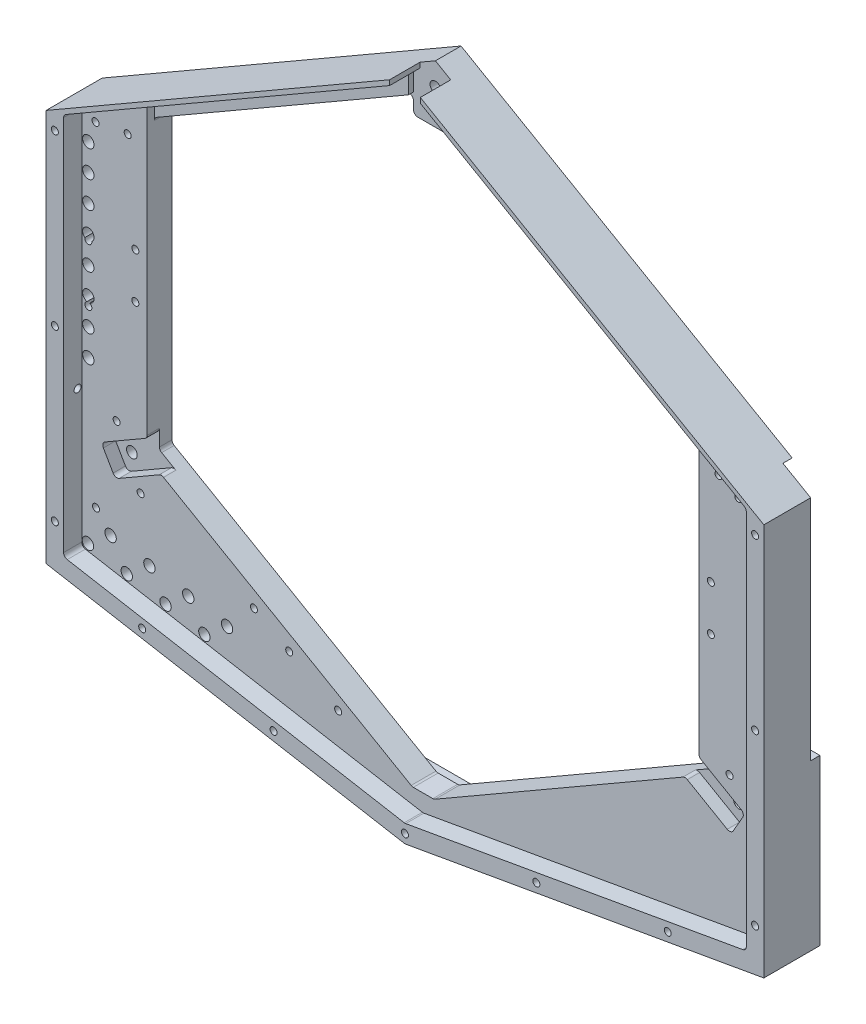
SolidWorks part; units mm, degrees
material "Copper"
ref_plane "Front Plane" through (0, 0, 0) normal (0, 0, 1) x (1, 0, 0)
ref_plane "Top Plane" through (0, 0, 0) normal (0, 1, 0) x (1, 0, 0)
ref_plane "Right Plane" through (0, 0, 0) normal (1, 0, 0) x (0, 0, -1)
sketch "Sketch2" plane through (0, 0, 0) normal (0, 0, 1) x (1, 0, 0)
  line L0 (-81.94, 26.6174) -> (0, 73.9255)
  line L1 (0, 73.9255) -> (81.94, 26.6174)
  line L2 (81.94, 26.6174) -> (81.94, -62.9963)
  line L3 (81.94, -62.9963) -> (0, -77.4445)
  line L4 (0, -77.4445) -> (-81.94, -62.9963)
  line L5 (-81.94, -62.9963) -> (-81.94, 26.6174)
  dimension "D1" = 120
  dimension "D2" = 120
  dimension "D3" = 160
  dimension "D4" = 151.37
  dimension "D5" = 163.88
extrude "Outline" add sketch "Sketch2" against normal blind 12.8
sketch "Sketch3" plane through (0, 0, 0) normal (0, 0, 1) x (1, 0, 0)
  line L0 (-77.94, 27.7721) -> (0, 72.7708)
  line L1 (0, 72.7708) -> (77.94, 27.7721)
  line L2 (77.94, 27.7721) -> (77.94, -59.6399)
  line L3 (77.94, -59.6399) -> (0, -73.3828)
  line L4 (0, -73.3828) -> (-77.94, -59.6399)
  line L5 (-77.94, -59.6399) -> (-77.94, 27.7721)
  line L12 (0, 73.9255) -> (-81.94, 26.6174) construction
  line L14 (0, -77.4445) -> (81.94, -62.9963) construction
  line L15 (-81.94, -62.9963) -> (0, -77.4445) construction
  line L16 (81.94, 26.6174) -> (0, 73.9255) construction
  line L17 (81.94, -62.9963) -> (81.94, 26.6174) construction
  line L18 (-81.94, 26.6174) -> (-81.94, -62.9963) construction
  dimension "D1" = 1
  dimension "D2" = 1
  dimension "D3" = 4
  dimension "D4" = 4
  dimension "D5" = 4
  dimension "D6" = 4
extrude "Inside Cutout" cut sketch "Sketch3" against normal blind 4.14
sketch "Reference Center Line" plane through (0, 0, -4.14) normal (0, 0, 1) x (1, 0, 0)
  line L0 (0, 73.9255) -> (0, -77.4445) construction
  line L1 (-62.3538, 35.1699) -> (0, 71.1699) construction
  line L2 (0, -70.1165) -> (62.3538, -34.1165) construction
  line L3 (62.3538, -34.1165) -> (62.3538, 37.8835) construction
  line L4 (62.3538, 37.8835) -> (0, 73.8835) construction
  line L5 (0, 73.8835) -> (-62.3538, 37.8835) construction
  line L6 (-62.3538, 37.8835) -> (-62.3538, -34.1165) construction
  line L7 (-62.3538, -34.1165) -> (0, -70.1165) construction
  line L8 (0, 71.1699) -> (62.3538, 35.1699) construction
  line L9 (-3.4641, 69.1699) -> (3.4641, 69.1699) construction
  line L11 (-46, 33.8928) -> (46, 33.8928) construction
  line L12 (-46, 33.8928) -> (-46, -62.2855) construction
  line L13 (-46, -62.2855) -> (46, -62.2855) construction
  line L14 (46, 33.8928) -> (46, -62.2855) construction
  circle A0 centre (0, 1.8835) radius 62.3538 construction
  circle A1 centre (0, 1.8835) radius 0.4741 construction
  point P22 (0, 33.8928)
  dimension "D1" = 72
  dimension "D2" = 72.042
  dimension "D3" = 2.35
  dimension "D4" = 2
  dimension "D5" = 92
sketch "Sketch5" plane through (0, 0, -12.8) normal (0, 0, -1) x (-1, 0, 0)
  line L0 (0, -70.8942) -> (-63, -34.5211)
  line L1 (-63, -34.5211) -> (-63, 31.7789)
  line L2 (5, 65.2652) -> (5, 69.884)
  line L3 (0, 0) -> (0, 50) construction
  line L6 (5, 69.884) -> (0, 72.7708)
  line L8 (0, 72.7708) -> (77.94, 27.7721) construction
  line L9 (63, 31.7789) -> (63, -34.5211)
  line L10 (63, -34.5211) -> (0, -70.8942)
  line L11 (0, 72.7708) -> (-5, 69.884)
  line L21 (5, 65.2652) -> (63, 31.7789)
  line L32 (0, 73.9255) -> (0, -77.4445) construction
  line L33 (-5, 69.884) -> (-5, 65.2652)
  line L34 (-77.94, 27.7721) -> (0, 72.7708) construction
  line L35 (-63, 31.7789) -> (-5, 65.2652)
  line L36 (0, 73.9255) -> (0, 1.8855) construction
  line L37 (0, 1.8855) -> (69.308, -38.1295) construction
  line L38 (0, 1.8855) -> (-69.308, -38.1295) construction
  dimension "D1" = 4
  dimension "D2" = 10
  dimension "D3" = 126
  dimension "D4" = 66.3
  dimension "D5" = 66.3
  dimension "D6" = 5
  dimension "D7" = 50
  dimension "D8" = 72.04
  dimension "D9" = 120
  dimension "D10" = 120
  dimension "D11" = 80.03
  dimension "D12" = 80.03
extrude "Cut for Spring Base" cut sketch "Sketch5" against normal through all
sketch "Sketch7" plane through (0, 0, -12.8) normal (0, 0, -1) x (-1, 0, 0)
  line L0 (-5, 69.884) -> (0, 72.7708)
  line L2 (0, 72.7708) -> (5, 69.884)
  line L4 (5, 69.884) -> (5, 60.7708)
  line L5 (5, 60.7708) -> (-5, 60.7708)
  line L6 (-5, 60.7708) -> (-5, 69.884)
  line L7 (-77.94, 27.7721) -> (0, 72.7708) construction
  line L8 (0, 73.9255) -> (0, -77.4445) construction
  line L9 (-77.94, 27.7721) -> (-5, 69.884) construction
  line L10 (5, 69.884) -> (77.94, 27.7721) construction
  dimension "D2" = 12
  dimension "D3" = 10
extrude "J Flex Mounting Point" add sketch "Sketch7" against normal offset from surface (5.85 mm away) 2.81 up to face at (0, 4.0573, -4.14)
sketch "Sketch6" plane through (0, 0, -12.8) normal (0, 0, -1) x (-1, 0, 0)
  line L0 (-67.5, 33.7996) -> (-67.5, -37.6965)
  line L2 (10, -70.8942) -> (67.5, -37.6965)
  line L3 (67.5, -37.6965) -> (67.5, 33.7996)
  line L9 (-10, -70.8942) -> (0, -70.8942)
  line L10 (-63, 31.7789) -> (-63, -34.5211) construction
  line L11 (63, -34.5211) -> (63, 31.7789) construction
  line L12 (0, -70.8942) -> (63, -34.5211) construction
  line L19 (67.5, 33.7996) -> (0, 72.7708)
  line L20 (77.94, 27.7721) -> (0, 72.7708) construction
  line L21 (0, 72.7708) -> (-77.94, 27.7721) construction
  line L22 (0, 72.7708) -> (-67.5, 33.7996)
  line L47 (0, -70.8942) -> (10, -70.8942)
  line L48 (-67.5, -37.6965) -> (-10, -70.8942)
  line L50 (-63, -34.5211) -> (0, -70.8942) construction
  line L52 (0, 73.9255) -> (0, -77.4445) construction
  dimension "D1" = 4.5
  dimension "D2" = 4.5
  dimension "D3" = 5
  dimension "D4" = 5
extrude "Spring Base Mounting Cut" cut sketch "Sketch6" against normal blind 3
sketch "Sketch9" plane through (0, 0, 0) normal (0, 0, 1) x (1, 0, 0)
  line L2 (3.5, 71.9048) -> (3.5, 70.7501)
  line L3 (77.94, 27.7721) -> (0, 72.7708) construction
  line L4 (3.5, 70.7501) -> (0, 72.7708)
  line L5 (0, 72.7708) -> (-3.5, 70.7501)
  line L6 (0, 72.7708) -> (-77.94, 27.7721) construction
  line L7 (-3.5, 70.7501) -> (-3.5, 71.9048)
  line L10 (-3.5, 71.9048) -> (0, 73.9255)
  line L11 (0, 73.9255) -> (0, -77.4445) construction
  line L12 (0, 73.9255) -> (3.5, 71.9048)
  line L14 (0, 73.9255) -> (-81.94, 26.6174) construction
  dimension "D1" = 7
extrude "Central Copper Flex cutout" cut sketch "Sketch9" against normal up to surface (6.95 mm away) up to face at (0, 66.373, -6.95)
hole_wizard "M2 Tap Drill for Backplate" positions "Sketch10" profile "Sketch11" hole size "M2x0.4" standard "ANSI Metric"
sketch "Sketch10" plane through (0, 0, -9.8) normal (0, 0, -1) x (-1, 0, 0)
  line L0 (-65, 24.3042) -> (-65, -35.6758) construction
  line L1 (-65, -35.6758) -> (-4, -70.8942) construction
  line L2 (-10, -70.8942) -> (10, -70.8942) construction
  line L4 (4, -70.8942) -> (65, -35.6758) construction
  line L5 (65, -35.6758) -> (65, 24.3242) construction
  line L7 (-63, -34.5211) -> (-63, 31.7789) construction
  line L8 (63, 31.7789) -> (63, -34.5211) construction
  line L9 (63, -34.5211) -> (0, -70.8942) construction
  line L10 (0, -70.8942) -> (-63, -34.5211) construction
  line L29 (-62.3538, 33.884) -> (0, 69.884) construction
  line L30 (-62.3538, -34.1165) -> (-62.3538, 37.8835) construction
  line L31 (0, 73.9255) -> (0, -77.4445) construction
  line L32 (0, 69.884) -> (62.3538, 33.884) construction
  line L33 (62.3538, 37.8835) -> (62.3538, -34.1165) construction
  line L36 (5, 65.2652) -> (63, 31.7789) construction
  line L37 (-63, 31.7789) -> (-5, 65.2652) construction
  line L38 (-63, -34.5211) -> (-67.5, -37.6965) construction
  point P0 (-65, 24.3042)
  point P2 (-41.1362, 46.134)
  point P4 (-19.4856, 58.634)
  point P6 (19.4856, 58.634)
  point P8 (41.1362, 46.134)
  point P10 (65, 24.3242)
  point P12 (65, 1.8242)
  point P14 (65, -20.6758)
  point P18 (52.0096, -43.1758)
  point P20 (32.9571, -54.1758)
  point P22 (15.6366, -64.1758)
  point P24 (-15.6366, -64.1758)
  point P26 (-32.9571, -54.1758)
  point P28 (-52.0096, -43.1758)
  point P32 (-65, -20.6958)
  point P35 (-65, 1.8042)
  dimension "D1" = 2
  dimension "D2" = 2
  dimension "D3" = 2
  dimension "D4" = 2
  dimension "D5" = 14.98
  dimension "D6" = 22.5
  dimension "D7" = 22.5
  dimension "D8" = 15
  dimension "D9" = 22
  dimension "D10" = 20
  dimension "D11" = 20
  dimension "D12" = 22
  dimension "D13" = 15
  dimension "D14" = 22.5
  dimension "D15" = 22.5
  dimension "D16" = 15
  dimension "D17" = 1.5
  dimension "D18" = 22.5
  dimension "D19" = 25
  dimension "D20" = 22.5
  dimension "D21" = 25
sketch "Sketch11" plane through (65, 24.3042, -9.8) normal (1, 0, 0) x (0, 1, 0)
  line L0 (0, 0) -> (0, 3.9807)
  line L1 (0, 3.9807) -> (0.8, 3.5)
  line L2 (0.8, 3.5) -> (0.8, 0)
  line L5 (0.8, 0) -> (0, 0)
  line L10 (0, 3.9807) -> (-0.8, 3.5) construction
  line L11 (0, -6.35) -> (0, 107.95) construction
  dimension "Hole Dia." = 1.6
  dimension "Hole Depth" = 3.5
  dimension "Drill Angle" = 118
sketch "Sketch12" plane through (0, 0, -12.8) normal (0, 0, -1) x (-1, 0, 0)
  line L0 (10, -70.8942) -> (67.5, -37.6965) construction
  line L1 (64, -39.7172) -> (67.5, -37.6965)
  line L2 (67.5, -37.6965) -> (67.5, -33.6551)
  line L3 (67.5, -37.6965) -> (67.5, 33.7996) construction
  line L4 (67.5, -33.6551) -> (74.4462, -37.6654)
  line L5 (74.4462, -37.6654) -> (70.9462, -43.7276)
  line L6 (70.9462, -43.7276) -> (64, -39.7172)
  line L7 (-67.5, -33.6551) -> (-67.5, -37.6965)
  line L8 (-67.5, 33.7996) -> (-67.5, -37.6965) construction
  line L9 (-67.5, -37.6965) -> (-64, -39.7172)
  line L10 (-67.5, -37.6965) -> (-10, -70.8942) construction
  line L11 (-64, -39.7172) -> (-70.9462, -43.7276)
  line L12 (-70.9462, -43.7276) -> (-74.4462, -37.6654)
  line L13 (-74.4462, -37.6654) -> (-67.5, -33.6551)
  dimension "D1" = 60
  dimension "D2" = 6
  dimension "D3" = 7
  dimension "D4" = 6
  dimension "D5" = 7
extrude "Outer Copper Flex cutouts" cut sketch "Sketch12" against normal up to surface (3 mm away) up to face at (64.2, 24.3042, -9.8)
hole_wizard "#2 Clearance Holes for Flex Feet" positions "Sketch13" profile "Sketch14" hole size "#2" standard "ANSI Inch" end condition up to next
sketch "Sketch13" plane through (0, 0, -9.8) normal (0, 0, -1) x (-1, 0, 0)
  line L1 (0, 1.8835) -> (69.3037, -38.129) construction
  line L3 (0, 1.8835) -> (-69.308, -38.1315) construction
  line L5 (0, 73.9255) -> (0, -77.4445) construction
  point P0 (69.3037, -38.129)
  point P3 (-69.308, -38.1315)
  point P6 (0, 68.6855)
  dimension "D1" = 66.802
  dimension "D2" = 80.025
  dimension "D3" = 60
  dimension "D4" = 60
  dimension "D5" = 80.03
sketch "Sketch14" plane through (-69.3037, -38.129, -9.8) normal (1, 0, 0) x (0, 1, 0)
  line L0 (0, 0) -> (0, 5.66)
  line L1 (0, 5.66) -> (1.2192, 5.66)
  line L2 (1.2192, 5.66) -> (1.2192, 0)
  line L5 (1.2192, 0) -> (0, 0)
  line L11 (0, -6.35) -> (0, 107.95) construction
  dimension "Thru Hole Dia." = 2.4384
  dimension "Thru Hole Depth" = 5.66
sketch "Sketch15" plane through (0, 0, -4.14) normal (0, 0, 1) x (1, 0, 0)
  line L0 (-63, -30.7945) -> (-73.5018, -36.8577)
  line L1 (-63, 31.7789) -> (-63, -34.5211) construction
  line L2 (-73.5018, -36.8577) -> (-70.2745, -42.4476)
  line L3 (-70.2745, -42.4476) -> (-59.7727, -36.3844)
  line L4 (-63, -34.5211) -> (0, -70.8942) construction
  line L5 (-59.7727, -36.3844) -> (-63, -34.5211)
  line L6 (-63, -34.5211) -> (-63, -30.7945)
  line L7 (-64.6136, -31.7262) -> (-61.3864, -37.316) construction
  line L8 (63, -34.5211) -> (63, -30.8575)
  line L9 (63, -34.5211) -> (63, 31.7789) construction
  line L10 (63, -30.8575) -> (73.4788, -36.9075)
  line L11 (73.4788, -36.9075) -> (70.3061, -42.4028)
  line L12 (70.3061, -42.4028) -> (59.8273, -36.3529)
  line L13 (0, -70.8942) -> (63, -34.5211) construction
  line L14 (59.8273, -36.3529) -> (63, -34.5211)
  point P12 (-63, -34.5211)
  dimension "D1" = 3.2
  dimension "D2" = 3
  dimension "D3" = 3.2
  dimension "D4" = 3
extrude "Channels for Outer Flex" cut sketch "Sketch15" against normal up to surface (2.81 mm away) up to face at (1.2192, 68.6855, -6.95)
sketch "Sketch17" plane through (0, 0, -9.8) normal (0, 0, -1) x (-1, 0, 0)
  line L0 (-65, 1.8042) -> (-65, -20.6958) construction
  line L1 (65, -20.6758) -> (65, 1.8242) construction
  circle A0 centre (-65, -9.4458) radius 0.8
  circle A1 centre (65, -9.4258) radius 0.8
  dimension "D1" = 1.6
  dimension "D2" = 1.6
extrude "Optional Alignment Pins" cut sketch "Sketch17" against normal blind 3
sketch "SMA Reference Sketch" plane through (0, 0, -12.8) normal (0, 0, -1) x (-1, 0, 0)
  line L14 (81.94, 26.6174) -> (81.94, -62.9963) construction
  line L21 (73.8944, 19.163) -> (78.9856, 14.0718) construction
  line L22 (73.8944, 23.663) -> (78.9856, 18.5718) construction
  line L23 (73.8944, 14.663) -> (78.9856, 9.5718) construction
  line L24 (73.8944, 10.163) -> (78.9856, 5.0718) construction
  line L25 (72.1444, -32.8014) -> (77.2356, -37.8926) construction
  line L26 (-73.8944, 20.0718) -> (-78.9856, 25.163) construction
  line L27 (-81.94, -62.9963) -> (-81.94, 26.6174) construction
  line L28 (-73.8944, 15.5718) -> (-78.9856, 20.663) construction
  line L29 (-73.8944, 11.0718) -> (-78.9856, 16.163) construction
  line L30 (-73.8944, 6.5718) -> (-78.9856, 11.663) construction
  line L31 (59.1444, -57.3926) -> (64.2356, -52.3014) construction
  line L32 (72.1444, -50.8926) -> (77.2356, -45.8014) construction
  line L33 (72.1444, -93.8926) -> (77.2356, -88.8014) construction
  line L34 (-73.8944, 2.0718) -> (-78.9856, 7.163) construction
  line L35 (-73.8944, -2.4282) -> (-78.9856, 2.663) construction
  line L36 (-73.8944, -6.9282) -> (-78.9856, -1.837) construction
  line L37 (-73.8944, -11.4282) -> (-78.9856, -6.337) construction
  line L38 (73.8944, 5.663) -> (78.9856, 0.5718) construction
  line L39 (73.8944, 1.163) -> (78.9856, -3.9282) construction
  line L40 (73.8944, -3.337) -> (78.9856, -8.4282) construction
  line L41 (73.8944, -7.837) -> (78.9856, -12.9282) construction
  circle A0 centre (73.8944, 23.663) radius 0.95 construction
  circle A1 centre (78.9856, 18.5718) radius 0.95 construction
  circle A2 centre (76.44, 21.1174) radius 1.3 construction
  circle A3 centre (73.8944, 19.163) radius 0.95 construction
  circle A4 centre (78.9856, 14.0718) radius 0.95 construction
  circle A5 centre (76.44, 16.6174) radius 1.3 construction
  circle A6 centre (73.8944, 14.663) radius 0.95 construction
  circle A7 centre (78.9856, 9.5718) radius 0.95 construction
  circle A8 centre (76.44, 12.1174) radius 1.3 construction
  circle A9 centre (73.8944, 10.163) radius 0.95 construction
  circle A10 centre (78.9856, 5.0718) radius 0.95 construction
  circle A11 centre (76.44, 7.6174) radius 1.3 construction
  circle A12 centre (72.1444, -32.8014) radius 0.95 construction
  circle A13 centre (77.2356, -37.8926) radius 0.95 construction
  circle A14 centre (74.69, -35.347) radius 1.3 construction
  circle A15 centre (-76.44, 22.6174) radius 1.3 construction
  circle A16 centre (-78.9856, 25.163) radius 0.95 construction
  circle A17 centre (-73.8944, 20.0718) radius 0.95 construction
  circle A18 centre (-76.44, 18.1174) radius 1.3 construction
  circle A19 centre (-78.9856, 20.663) radius 0.95 construction
  circle A20 centre (-73.8944, 15.5718) radius 0.95 construction
  circle A21 centre (-76.44, 13.6174) radius 1.3 construction
  circle A22 centre (-78.9856, 16.163) radius 0.95 construction
  circle A23 centre (-73.8944, 11.0718) radius 0.95 construction
  circle A24 centre (-76.44, 9.1174) radius 1.3 construction
  circle A25 centre (-78.9856, 11.663) radius 0.95 construction
  circle A26 centre (-73.8944, 6.5718) radius 0.95 construction
  circle A27 centre (61.69, -54.847) radius 1.3 construction
  circle A28 centre (64.2356, -52.3014) radius 0.95 construction
  circle A29 centre (59.1444, -57.3926) radius 0.95 construction
  circle A30 centre (72.1444, -50.8926) radius 0.95 construction
  circle A31 centre (77.2356, -45.8014) radius 0.95 construction
  circle A32 centre (74.69, -48.347) radius 1.3 construction
  circle A33 centre (74.69, -91.347) radius 1.3 construction
  circle A34 centre (77.2356, -88.8014) radius 0.95 construction
  circle A35 centre (72.1444, -93.8926) radius 0.95 construction
  circle A36 centre (74.69, -35.347) radius 43 construction
  circle A37 centre (74.69, -48.347) radius 13 construction
  circle A38 centre (61.69, -54.847) radius 43 construction
  circle A39 centre (74.69, -91.347) radius 43 construction
  circle A40 centre (76.44, 21.1174) radius 13 construction
  circle A41 centre (-76.44, 4.6174) radius 1.3 construction
  circle A42 centre (-78.9856, 7.163) radius 0.95 construction
  circle A43 centre (-73.8944, 2.0718) radius 0.95 construction
  circle A44 centre (-76.44, 0.1174) radius 1.3 construction
  circle A45 centre (-78.9856, 2.663) radius 0.95 construction
  circle A46 centre (-73.8944, -2.4282) radius 0.95 construction
  circle A47 centre (-76.44, -4.3826) radius 1.3 construction
  circle A48 centre (-78.9856, -1.837) radius 0.95 construction
  circle A49 centre (-73.8944, -6.9282) radius 0.95 construction
  circle A50 centre (-76.44, -8.8826) radius 1.3 construction
  circle A51 centre (-78.9856, -6.337) radius 0.95 construction
  circle A52 centre (-73.8944, -11.4282) radius 0.95 construction
  circle A53 centre (73.8944, 5.663) radius 0.95 construction
  circle A54 centre (78.9856, 0.5718) radius 0.95 construction
  circle A55 centre (76.44, 3.1174) radius 1.3 construction
  circle A56 centre (73.8944, 1.163) radius 0.95 construction
  circle A57 centre (78.9856, -3.9282) radius 0.95 construction
  circle A58 centre (76.44, -1.3826) radius 1.3 construction
  circle A59 centre (73.8944, -3.337) radius 0.95 construction
  circle A60 centre (78.9856, -8.4282) radius 0.95 construction
  circle A61 centre (76.44, -5.8826) radius 1.3 construction
  circle A62 centre (73.8944, -7.837) radius 0.95 construction
  circle A63 centre (78.9856, -12.9282) radius 0.95 construction
  circle A64 centre (76.44, -10.3826) radius 1.3 construction
  point P10 (76.44, 16.6174)
  point P20 (76.44, 21.1174)
  point P25 (76.44, 12.1174)
  point P32 (76.44, 7.6174)
  point P37 (74.69, -35.347)
  point P120 (76.44, 3.1174)
  point P127 (76.44, -1.3826)
  point P134 (76.44, -5.8826)
  point P141 (76.44, -10.3826)
  dimension "D5" = 1.9
  dimension "D2" = 2.6
  dimension "D3" = 8
  dimension "D10" = 2.6
  dimension "D11" = 1.9
  dimension "D12" = 1.9
  dimension "D18" = 26
  dimension "D23" = 86
  dimension "D26" = 4.5
  dimension "D27" = 4.5
  dimension "D28" = 4.5
  dimension "D29" = 43
  dimension "D30" = 13
  dimension "D31" = 26
  dimension "D1" = 7.2
  dimension "D4" = 4.5
  dimension "D6" = 5.5
  dimension "D7" = 5.5
  dimension "D8" = 45
  dimension "D9" = 7.25
  dimension "D13" = 7.2
  dimension "D14" = 5.5
  dimension "D15" = 4
  dimension "D16" = 45
  dimension "D19" = 7.25
  dimension "D20" = 45
  dimension "D21" = 4.5
  dimension "D22" = 7.25
  dimension "D24" = 13
  dimension "D25" = 43
  dimension "D17" = 8
sketch "Sketch19" plane through (0, 0, -12.8) normal (0, 0, -1) x (-1, 0, 0)
  line L1 (81.94, -62.9963) -> (0, -77.4445) construction
  circle A0 centre (76.44, 21.1174) radius 1.3
  circle A12 centre (-76.44, 22.6174) radius 1.3
  circle A22 centre (-76.44, 16.5174) radius 1.3
  circle A23 centre (-76.44, 10.4174) radius 1.3
  circle A24 centre (-76.44, 4.3174) radius 1.3
  circle A25 centre (-76.44, -1.7826) radius 1.3
  circle A26 centre (-76.44, -7.8826) radius 1.3
  circle A27 centre (-76.44, -13.9826) radius 1.3
  circle A28 centre (-76.44, -20.0826) radius 1.3
  circle A29 centre (76.44, 15.0174) radius 1.3
  circle A30 centre (76.44, 8.9174) radius 1.3
  circle A31 centre (76.44, 2.8174) radius 1.3
  circle A32 centre (76.44, -3.2826) radius 1.3
  circle A33 centre (76.44, -9.3826) radius 1.3
  circle A34 centre (76.44, -15.4826) radius 1.3
  circle A35 centre (76.44, -21.5826) radius 1.3
  circle A36 centre (49.94, -63.0539) radius 1.3
  circle A44 centre (44.763, -58.8896) radius 1.3
  circle A50 centre (53.6263, -57.3268) radius 1.3
  circle A51 centre (58.8033, -61.4911) radius 1.3
  circle A52 centre (62.4895, -55.7639) radius 1.3
  circle A53 centre (67.6665, -59.9282) radius 1.3
  circle A54 centre (71.3528, -54.2011) radius 1.3
  circle A55 centre (76.5298, -58.3654) radius 1.3
  dimension "D1" = 2.6
  dimension "D2" = 8
  dimension "D3" = 8
  dimension "D4" = 5.5
  dimension "D5" = 32
  dimension "D6" = 4
  dimension "D7" = 10.5
  dimension "D8" = 6.644
extrude "SMA_Lines" cut sketch "Sketch19" against normal up to next
sketch "Sketch20" plane through (0, 0, -12.8) normal (0, 0, -1) x (-1, 0, 0)
  line L0 (67.5, 23.8447) -> (73.0812, 29.4259)
  line L1 (67.5, -33.6551) -> (67.5, 33.7996) construction
  line L2 (42.44, -52.1649) -> (37.6769, -54.9149)
  line L3 (73.0812, 29.4259) -> (81.94, 20.5672)
  line L4 (81.94, 20.5672) -> (81.94, -62.9963)
  line L5 (81.94, -62.9963) -> (42.44, -69.9612)
  line L6 (81.94, -62.9963) -> (0, -77.4445) construction
  line L8 (10, -70.8942) -> (64, -39.7172) construction
  line L9 (10, -70.8942) -> (64, -39.7172) construction
  line L10 (42.44, -52.1649) -> (64, -39.7172)
  line L11 (64, -39.7172) -> (67.5, -33.6551)
  line L12 (67.5, -33.6551) -> (74.4462, -37.6654) construction
  line L13 (67.5, -33.6551) -> (67.5, 23.8447)
  line L14 (-75.6096, 30.2723) -> (-67.5, 22.1627)
  line L15 (-81.94, 26.6174) -> (0, 73.9255) construction
  line L16 (-67.5, 33.7996) -> (-67.5, -33.6551) construction
  line L17 (-67.5, 22.1627) -> (-67.5, -25.3826)
  line L18 (-67.5, -25.3826) -> (-81.94, -25.3826)
  line L20 (-81.94, -62.9963) -> (-81.94, 26.6174) construction
  line L21 (-81.94, -25.3826) -> (-81.94, 26.6174)
  line L22 (-81.94, 26.6174) -> (-75.6096, 30.2723)
  line L23 (73.8944, 23.663) -> (78.9856, 18.5718) construction
  line L24 (-73.8944, 20.0718) -> (-78.9856, 25.163) construction
  line L25 (37.6769, -54.9149) -> (37.6769, -58.9149)
  line L26 (37.6769, -58.9149) -> (42.44, -58.9149)
  line L28 (42.44, -58.9149) -> (42.44, -69.9612)
  dimension "D2" = 8.25
  dimension "D3" = 6
  dimension "D4" = 34.5
  dimension "D5" = 3.5
extrude "SMA Cutaway" cut sketch "Sketch20" against normal offset from surface (2.11 mm away) 6.55 up to face at (77.74, 22.6174, -4.14)
fillet "Fillet4" radius 3 2 edges at (-73.0812, 29.4259, -11.745) (-37.6769, -58.9149, -11.745)
hole_wizard "M2x0.4 Tapped for SMAs" positions "Sketch21" profile "Sketch22" hole size "M2x0.4" standard "ANSI Metric"
sketch "Sketch21" plane through (0, 0, -10.69) normal (0, 0, -1) x (-1, 0, 0)
  circle A0 centre (76.44, 21.1174) radius 1.3 construction
  circle A1 centre (-76.44, 22.6174) radius 1.3 construction
  circle A2 centre (49.94, -63.0539) radius 1.3 construction
  circle A3 centre (44.763, -58.8896) radius 1.3 construction
  point P72 (73.895, 23.6624)
  point P74 (78.985, 18.5724)
  point P90 (-78.985, 25.1624)
  point P92 (-73.895, 20.0724)
  point P108 (-78.985, 19.0624)
  point P109 (-73.895, 13.9724)
  point P110 (-78.985, 12.9624)
  point P111 (-73.895, 7.8724)
  point P112 (-78.985, 6.8624)
  point P113 (-73.895, 1.7724)
  point P114 (-78.985, 0.7624)
  point P115 (-73.895, -4.3276)
  point P116 (-78.985, -5.3376)
  point P117 (-73.895, -10.4276)
  point P118 (-78.985, -11.4376)
  point P119 (-73.895, -16.5276)
  point P120 (-78.985, -17.5376)
  point P121 (-73.895, -22.6276)
  point P138 (73.895, 17.5624)
  point P139 (78.985, 12.4724)
  point P140 (73.895, 11.4624)
  point P141 (78.985, 6.3724)
  point P142 (73.895, 5.3624)
  point P143 (78.985, 0.2724)
  point P144 (73.895, -0.7376)
  point P145 (78.985, -5.8276)
  point P146 (73.895, -6.8376)
  point P147 (78.985, -11.9276)
  point P148 (73.895, -12.9376)
  point P149 (78.985, -18.0276)
  point P150 (73.895, -19.0376)
  point P151 (78.985, -24.1276)
  point P171 (49.315, -59.5089)
  point P173 (50.565, -66.5989)
  point P185 (58.1783, -57.9461)
  point P186 (59.4283, -65.0361)
  point P187 (67.0415, -56.3832)
  point P188 (68.2915, -63.4732)
  point P189 (75.9048, -54.8204)
  point P190 (77.1548, -61.9104)
  point P191 (45.388, -62.4346)
  point P193 (44.138, -55.3446)
  point P202 (54.2513, -60.8718)
  point P203 (53.0013, -53.7818)
  point P204 (63.1145, -59.3089)
  point P205 (61.8645, -52.2189)
  point P206 (71.9778, -57.7461)
  point P207 (70.7278, -50.6561)
  dimension "D4" = 2.545
  dimension "D7" = 2.545
  dimension "D8" = 2.545
  dimension "D9" = 8
  dimension "D14" = 0.625
  dimension "D1" = 2.545
  dimension "D2" = 2.545
  dimension "D3" = 2.545
  dimension "D5" = 2.545
  dimension "D6" = 2.545
  dimension "D11" = 3.545
  dimension "D12" = 0.625
  dimension "D13" = 3.545
  dimension "D16" = 3.545
  dimension "D17" = 0.625
  dimension "D18" = 0.625
  dimension "D19" = 3.545
  dimension "D10" = 8
  dimension "D15" = 4
sketch "Sketch22" plane through (-73.895, 23.6624, -10.69) normal (1, 0, 0) x (0, 1, 0)
  line L0 (0, 0) -> (0, 5.4807)
  line L1 (0, 5.4807) -> (0.8, 5)
  line L2 (0.8, 5) -> (0.8, 0)
  line L5 (0.8, 0) -> (0, 0)
  line L10 (0, 5.4807) -> (-0.8, 5) construction
  line L11 (0, -6.35) -> (0, 107.95) construction
  dimension "Hole Dia." = 1.6
  dimension "Hole Depth" = 5
  dimension "Drill Angle" = 118
sketch "Sketch23" plane through (0, 0, -4.14) normal (0, 0, 1) x (1, 0, 0)
  line L0 (-63, 31.7789) -> (-63, 36.3977)
  line L1 (-3.5, 70.7501) -> (-77.94, 27.7721) construction
  line L2 (-63, 36.3977) -> (-5, 69.884)
  line L3 (-5, 69.884) -> (-5, 65.2652)
  line L4 (-5, 65.2652) -> (-63, 31.7789)
  line L5 (5, 65.2652) -> (5, 69.884)
  line L6 (5, 65.2652) -> (63, 31.7789)
  line L7 (63, 31.7789) -> (63, 36.3977)
  line L8 (77.94, 27.7721) -> (5, 69.884) construction
  line L9 (63, 36.3977) -> (5, 69.884)
extrude "Slight Relief Under Array" cut sketch "Sketch23" against normal blind 1.66
hole_wizard "M2x0.4 Tapped for Radiation Cover" positions "Sketch24" profile "Sketch25" hole size "M2x0.4" standard "ANSI Metric"
sketch "Sketch24" plane through (0, 0, 0) normal (0, 0, 1) x (1, 0, 0)
  line L0 (-81.94, 26.6174) -> (-81.94, -62.9963) construction
  line L1 (-77.94, -59.6399) -> (0, -73.3828) construction
  line L2 (0, -73.3828) -> (77.94, -59.6399) construction
  line L3 (77.94, -59.6399) -> (77.94, 27.7721) construction
  line L4 (81.94, -62.9963) -> (81.94, 26.6174) construction
  line L5 (-79.94, 23.6174) -> (-79.94, -53.6399) construction
  line L6 (0, -77.4445) -> (0, -73.3828) construction
  line L7 (79.94, 23.6174) -> (79.94, -53.6399) construction
  line L8 (0, -73.3828) -> (77.94, -59.6399) construction
  point P0 (-79.94, 23.6174)
  point P2 (-79.94, -53.6399)
  point P4 (-30, -70.1239)
  point P6 (30, -70.1239)
  point P8 (79.94, -53.6399)
  point P10 (79.94, 23.6174)
  point P31 (-79.94, -15.0112)
  point P38 (0, -75.4137)
  point P44 (79.94, -15.0112)
  point P47 (-60, -64.834)
  point P49 (60, -64.834)
  dimension "D1" = 2
  dimension "D2" = 3
  dimension "D3" = 2
  dimension "D4" = 6
  dimension "D5" = 2
  dimension "D6" = 30
  dimension "D7" = 2
  dimension "D8" = 30
  dimension "D9" = 2
  dimension "D10" = 6
  dimension "D11" = 2
  dimension "D12" = 3
  dimension "D13" = 2
  dimension "D14" = 30
  dimension "D15" = 2
  dimension "D16" = 30
sketch "Sketch25" plane through (-79.94, 23.6174, 0) normal (1, 0, 0) x (0, -1, 0)
  line L0 (0, 0) -> (0, 5.4807)
  line L1 (0, 5.4807) -> (0.8, 5)
  line L2 (0.8, 5) -> (0.8, 0)
  line L5 (0.8, 0) -> (0, 0)
  line L10 (0, 5.4807) -> (-0.8, 5) construction
  line L11 (0, -6.35) -> (0, 107.95) construction
  dimension "Hole Dia." = 1.6
  dimension "Hole Depth" = 5
  dimension "Drill Angle" = 118
hole_wizard "M2x0.4 Tap for PCB Mounts" positions "Sketch26" profile "Sketch27" hole size "M2x0.4" standard "ANSI Metric"
sketch "Sketch26" plane through (0, 0, -4.14) normal (0, 0, 1) x (1, 0, 0)
  line L1 (76.44, 22.6174) -> (76.44, 2.1174) construction
  line L6 (74.69, -6.3826) -> (74.69, -18.8826) construction
  line L9 (-76.44, 21.1174) -> (-76.44, 8.1174) construction
  line L11 (-76.44, -4.8826) -> (-76.44, -17.8826) construction
  line L15 (-76.44, -11.3826) -> (-77.94, -11.3826) construction
  line L16 (-77.94, 27.7721) -> (-77.94, -59.6399) construction
  line L18 (-76.44, 14.6174) -> (-77.94, 14.6174) construction
  line L19 (-77.94, 27.7721) -> (-77.94, -59.6399) construction
  line L23 (-76.44, 8.1174) -> (-76.44, -4.8826) construction
  line L24 (-74.69, -56.8826) -> (-74.69, -43.8826) construction
  circle A6 centre (76.44, 22.6174) radius 1.3 construction
  circle A11 centre (-76.44, 21.1174) radius 1.3 construction
  point P0 (76.44, 12.3674)
  point P20 (76.44, 12.3674)
  point P31 (74.69, -12.6326)
  point P34 (74.69, -12.6326)
  point P53 (-76.44, 14.6174)
  point P55 (-76.44, -11.3826)
  point P57 (-74.69, -50.3826)
  point P59 (-19.3942, -62.8516)
  point P78 (-76.44, 14.6174)
  point P79 (-76.44, -11.3826)
  point P95 (-76.44, 1.6174)
  point P106 (-67.45, 27.1118)
  point P108 (-65.6984, 5.1456)
  point P110 (-65.6984, -5.1874)
  point P112 (-69.9656, -30.8826)
  point P114 (-64.5046, -42.4348)
  point P116 (-38.622, -52.2344)
  point P118 (-30.5702, -56.7556)
  point P140 (71.9662, 24.8501)
  point P150 (74.69, -0.1326)
  point P153 (69.97, -30.8826)
  point P159 (67.45, 27.1118)
  point P161 (65.7, 5.1456)
  point P163 (65.7, -5.1874)
  point P174 (-74.7882, 25.8367)
  dimension "D8" = 0.3048
  dimension "D11" = 10.1854
  dimension "D2" = 5
  dimension "D3" = 8.99
  dimension "D4" = 5.9944
  dimension "D7" = 2.9718
  dimension "8.99" = 8.99
  dimension "D22" = 0
  dimension "D23" = 5
sketch "Sketch27" plane through (76.44, 12.3674, -4.14) normal (1, 0, 0) x (0, -1, 0)
  line L0 (0, 0) -> (0, 5.1807)
  line L1 (0, 5.1807) -> (0.8, 4.7)
  line L2 (0.8, 4.7) -> (0.8, 0)
  line L5 (0.8, 0) -> (0, 0)
  line L10 (0, 5.1807) -> (-0.8, 4.7) construction
  line L11 (0, -6.35) -> (0, 107.95) construction
  dimension "Hole Dia." = 1.6
  dimension "Hole Depth" = 4.7
  dimension "Drill Angle" = 118
hole_wizard "Tap Drill for M3x0.5 Tap1" positions "Sketch28" profile "Sketch29" hole size "M3x0.5" standard "ANSI Metric"
sketch "Sketch28" plane through (0, 0, -12.8) normal (0, 0, -1) x (-1, 0, 0)
  line L0 (-69.3538, 29.7708) -> (69.3538, 29.7708) construction
  line L2 (-40, -61.4445) -> (40, -61.4445) construction
  line L4 (0, 73.9255) -> (0, -77.4445) construction
  line L6 (5, 60.7708) -> (-5, 60.7708) construction
  line L7 (-62.3538, -34.1165) -> (-62.3538, 37.8835) construction
  point P0 (-69.3538, 29.7708)
  point P2 (69.3538, 29.7708)
  point P4 (40, -61.4445)
  point P6 (-40, -61.4445)
  point P17 (0, 29.7708)
  point P20 (0, -61.4445)
  dimension "D1" = 40
  dimension "D2" = 16
  dimension "D3" = 7
  dimension "D4" = 31
sketch "Sketch29" plane through (69.3538, 29.7708, -12.8) normal (1, 0, 0) x (0, 1, 0)
  line L0 (0, 0) -> (0, 6.7511)
  line L1 (0, 6.7511) -> (1.25, 6)
  line L2 (1.25, 6) -> (1.25, 0)
  line L5 (1.25, 0) -> (0, 0)
  line L10 (0, 6.7511) -> (-1.25, 6) construction
  line L11 (0, -6.35) -> (0, 107.95) construction
  dimension "Hole Dia." = 2.5
  dimension "Hole Depth" = 6
  dimension "Drill Angle" = 118
hole_wizard "M2x0.4 Tap for Thermometer" positions "Sketch30" profile "Sketch31" hole size "M2x0.4" standard "ANSI Metric"
sketch "Sketch30" plane through (-81.94, 0, 0) normal (-1, 0, 0) x (0, 0, 1)
  line L0 (-10.69, -62.9963) -> (0, -62.9963) construction
  line L1 (-10.69, -62.9963) -> (-10.69, 20.5672) construction
  circle A0 centre (-3.19, -27.9963) radius 7.15 construction
  point P0 (-3.19, -27.9963)
  dimension "D1" = 35
  dimension "D2" = 7.5
sketch "Sketch31" plane through (-81.94, -27.9963, -3.19) normal (0, 1, 0) x (0, 0, 1)
  line L0 (0, 0) -> (0, 5.4807)
  line L1 (0, 5.4807) -> (0.8, 5)
  line L2 (0.8, 5) -> (0.8, 0)
  line L5 (0.8, 0) -> (0, 0)
  line L10 (0, 5.4807) -> (-0.8, 5) construction
  line L11 (0, -6.35) -> (0, 107.95) construction
  dimension "Hole Dia." = 1.6
  dimension "Hole Depth" = 5
  dimension "Drill Angle" = 118
fillet "Fillet1" radius 1 38 edges at (63, 36.3977, -4.97) (-63, 36.3977, -4.97) (-5, 69.884, -6.375) (5, 69.884, -6.375) (70.3061, -42.4028, -5.545) (73.4788, -36.9075, -5.545) (59.8273, -36.3529, -5.545) (63, -30.8575, -5.545) (77.94, 27.7721, -2.07) (77.94, -59.6399, -2.07) (0, -73.3828, -2.07) (-77.94, -59.6399, -2.07) (-70.2745, -42.4476, -5.545) (-59.7727, -36.3844, -5.545) (-63, -30.7945, -5.545) (-73.5018, -36.8577, -5.545) (67.5, 33.7996, -11.3) (63, 31.7789, -7.8) (-5, 65.2652, -8.375) (5, 65.2652, -8.375) (0, 72.7708, -11.3) (-63, 31.7789, -7.8) (-67.5, 33.7996, -11.3) (-67.5, -33.6551, -10.245) (-74.4462, -37.6654, -10.245) (-70.9462, -43.7276, -10.245) (-64, -39.7172, -10.245) (-63, -34.5211, -8.375) (-10, -70.8942, -11.3) (10, -70.8942, -11.3) (63, -34.5211, -8.375) (64, -39.7172, -11.3) (70.9462, -43.7276, -11.3) (74.4462, -37.6654, -11.3) (67.5, -33.6551, -11.3) (5, 60.7708, -8.375) (-5, 60.7708, -8.375) (-77.94, 27.7721, -2.07)
fillet "Fillet2" radius 5 1 edges at (0, -70.8942, -6.97)
sketch "Sketch32" plane through (0, 0, -9.8) normal (0, 0, -1) x (-1, 0, 0)
  circle A0 centre (65, 24.3242) radius 0.8 construction
  circle A1 centre (65, 1.8242) radius 0.8 construction
  circle A2 centre (65, -9.4258) radius 0.8 construction
  circle A3 centre (65, -20.6758) radius 0.8 construction
  circle A4 centre (52.0096, -43.1758) radius 0.8 construction
  circle A5 centre (32.9571, -54.1758) radius 0.8 construction
  circle A6 centre (15.6366, -64.1758) radius 0.8 construction
  circle A7 centre (-15.6366, -64.1758) radius 0.8 construction
  circle A8 centre (-32.9571, -54.1758) radius 0.8 construction
  circle A9 centre (-52.0096, -43.1758) radius 0.8 construction
  circle A10 centre (-65, -20.6958) radius 0.8 construction
  circle A11 centre (-65, 1.8042) radius 0.8 construction
  circle A12 centre (-65, 24.3042) radius 0.8 construction
  circle A13 centre (65, 24.3242) radius 0.8
  circle A14 centre (65, 1.8242) radius 0.8
  circle A15 centre (65, -9.4258) radius 0.8
  circle A16 centre (65, -20.6758) radius 0.8
  circle A17 centre (52.0096, -43.1758) radius 0.8
  circle A18 centre (32.9571, -54.1758) radius 0.8
  circle A19 centre (15.6366, -64.1758) radius 0.8
  circle A20 centre (-15.6366, -64.1758) radius 0.8
  circle A21 centre (-32.9571, -54.1758) radius 0.8
  circle A22 centre (-52.0096, -43.1758) radius 0.8
  circle A23 centre (-65, -20.6958) radius 0.8
  circle A24 centre (-65, 1.8042) radius 0.8
  circle A25 centre (-65, 24.3042) radius 0.8
fillet "Fillet5" radius 1 2 edges at (-2.5, -69.4508, -6.97) (2.5, -69.4508, -6.97)
fillet "Fillet6" radius 3 1 edges at (-42.44, -58.9149, -11.745)
